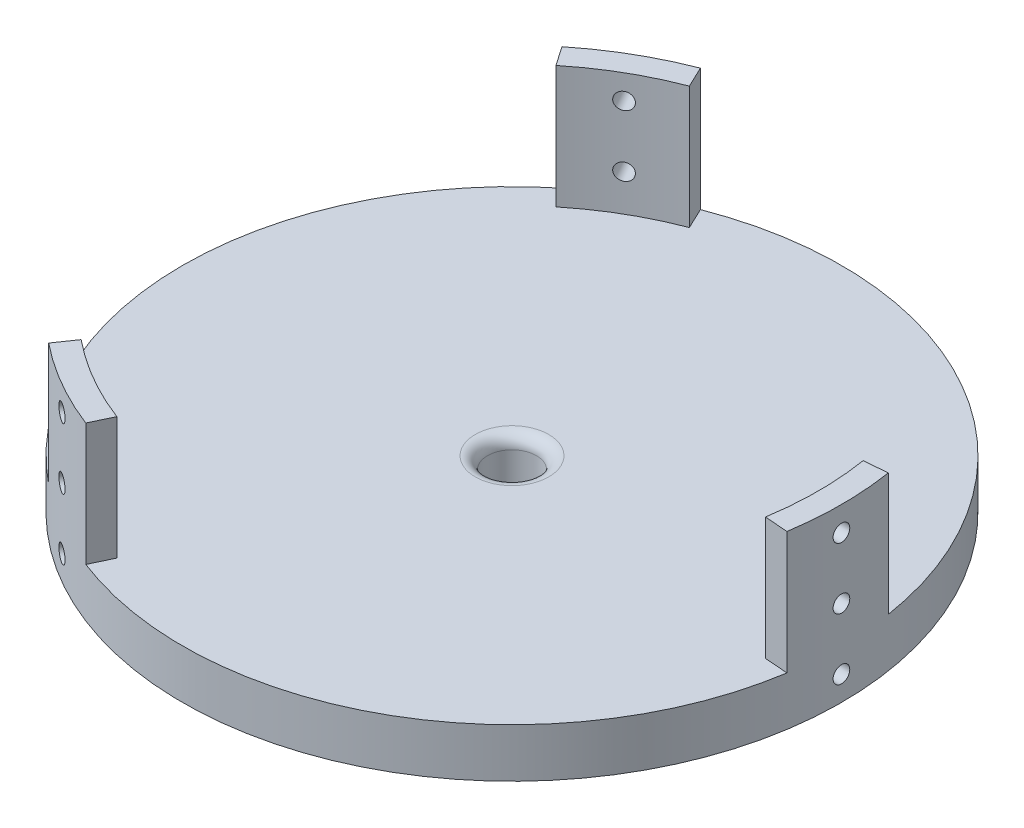
SolidWorks part; units mm, degrees
material "6061-T6 (SS)"
ref_plane "Front" through (0, 0, 0) normal (0, 0, 1) x (1, 0, 0)
ref_plane "Top" through (0, 0, 0) normal (0, 1, 0) x (1, 0, 0)
ref_plane "Right" through (0, 0, 0) normal (1, 0, 0) x (0, 0, -1)
sketch "Sketch1" plane through (0, 0, 0) normal (0, 1, 0) x (1, 0, 0)
  line L1 (0, 0) -> (127.635, 0)
  line L2 (0, 0) -> (0, 127.635)
  line L3 (0, 127.635) -> (127.635, 127.635)
  line L4 (127.635, 0) -> (127.635, 127.635)
  dimension "D1" = 127.635
  dimension "D2" = 127.635
extrude "Main Plate" add sketch "Sketch1" along normal blind 12.7
sketch "Sketch9" plane through (0, 12.7, 0) normal (0, 1, 0) x (1, 0, 0)
  circle A0 centre (63.8175, 63.8175) radius 85.725
  dimension "D1" = 171.45
extrude "Boss-Extrude1" add sketch "Sketch9" against normal up to surface (12.7 mm away) contours A0 up to face at (63.8175, 0, -63.8175)
sketch "Sketch10" plane through (0, 12.7, 0) normal (0, 1, 0) x (1, 0, 0)
  circle A0 centre (63.8175, 63.8175) radius 95.25
  circle A1 centre (63.8175, 63.8175) radius 85.4075
  dimension "D1" = 170.815
  dimension "D2" = 190.5
extrude "Cut-Extrude1" cut sketch "Sketch10" against normal blind 167.64 contours A0 | A1
sketch "Sketch14" plane through (0, 12.7, 0) normal (0, 1, 0) x (1, 0, 0)
  line L0 (201.1692, 63.8175) -> (-73.4523, 63.8175) construction
ref_plane "Plane1" through (0, 0, -63.8175) normal (0, 0, -1) x (-1, 0, 0)
ref_plane "Plane3" through (0, 6.35, 0) normal (0, 1, 0) x (1, 0, 0)
ref_plane "Plane2" through (-21.59, 0, 0) normal (-1, 0, 0) x (0, 0, 1)
sketch "Sketch18" plane through (0, 6.35, 0) normal (0, 1, 0) x (1, 0, 0)
  circle A0 centre (63.8175, 63.8175) radius 85.4075
  circle A1 centre (63.8175, 63.8175) radius 79.375
  circle A4 centre (63.8175, 63.8175) radius 85.4075 construction
  dimension "D1" = 158.75
extrude "Boss-Extrude2" add sketch "Sketch18" along normal blind 38.1
sketch "Sketch20" plane through (0, 12.7, 0) normal (0, 1, 0) x (1, 0, 0)
  line L0 (63.8175, 143.1925) -> (63.8175, -15.5575) construction
  line L1 (-15.5575, 63.8175) -> (143.1925, 63.8175) construction
  line L2 (63.8175, 63.8175) -> (-15.5575, -73.664) construction
  circle A0 centre (63.8175, 63.8175) radius 79.375 construction
  dimension "D1" = 30
ref_plane "Plane5" through (-15.5575, 12.7, 73.664) normal (-0.5, 0, 0.866) x (0.866, 0, 0.5)
sketch "Sketch15" plane through (166.2216, 0, 178.6143) normal (0.5, 0, -0.866) x (-0.866, 0, -0.5)
  line L3 (289.2754, 44.45) -> (130.5254, 44.45) construction
  line L4 (124.4929, 0) -> (295.3079, 0) construction
  line L6 (278.6412, 12.7) -> (141.1597, 12.7) construction
  circle A0 centre (209.9004, 22.225) radius 2.159
  circle A1 centre (209.9004, 38.1) radius 2.159
  circle A2 centre (209.9004, 6.35) radius 2.159
  point P16 (209.9004, 12.7)
  dimension "D1" = 4.318
  dimension "D2" = 15.875
  dimension "D3" = 4.318
  dimension "D4" = 4.318
  dimension "D5" = 6.35
  dimension "D6" = 6.35
  dimension "D7" = 0
extrude "Cut-Extrude3" cut sketch "Sketch15" along normal blind 88.9
pattern_circular "CirPattern1" count 3 over 360 about axis through (63.8175, -154.94, -63.8175) along (0, 1, 0) of "Cut-Extrude3" reverse direction yes
ref_plane "Plane4" through (63.8175, 0, 0) normal (-1, 0, 0) x (0, 0, 1)
sketch "Sketch23" plane through (0, 12.7, 0) normal (0, 1, 0) x (1, 0, 0)
  line L0 (13.6787, 125.352) -> (7.5523, 134.2379)
  line L1 (15.1867, 11.8815) -> (13.6787, 2.283) construction
  line L3 (-15.5575, 63.8175) -> (143.1925, 63.8175) construction
  line L4 (63.8175, 143.1925) -> (63.8175, -15.5575) construction
  line L5 (-15.5575, 63.8175) -> (143.1925, 63.8175)
  line L6 (63.8175, 143.1925) -> (63.8175, -15.5575)
  line L7 (13.6787, 2.283) -> (6.9592, -7.4631)
  line L8 (-19.2671, 125.3206) -> (-48.797, 60.3978)
  line L9 (-48.797, 60.3978) -> (-9.8843, 7.0525)
  line L10 (-9.8843, 7.0525) -> (6.9592, -7.4631)
  line L11 (24.1345, -4.9259) -> (13.6787, 2.283) construction
  line L14 (7.5523, 134.2379) -> (-19.2671, 125.3206)
  line L15 (24.1345, 132.5609) -> (13.6787, 125.352) construction
  line L28 (63.8175, 63.8175) -> (24.1345, -4.9259) construction
  line L29 (63.8175, 63.8175) -> (24.1345, 132.5609) construction
  line L30 (142.1773, 76.4717) -> (152.9359, 77.3344)
  line L31 (152.9359, 77.3344) -> (158.6231, 105.0193)
  line L32 (158.6231, 105.0193) -> (117.1632, 163.0543)
  line L33 (117.1632, 163.0543) -> (51.5085, 156.0277)
  line L34 (51.5085, 156.0277) -> (30.5159, 148.6985)
  line L35 (35.5964, 138.0062) -> (30.5159, 148.6985)
  line L36 (35.5964, -10.3712) -> (30.9643, -20.1198)
  line L37 (30.9643, -20.1198) -> (52.0965, -38.8874)
  line L38 (52.0965, -38.8874) -> (123.0863, -31.9996)
  line L39 (123.0863, -31.9996) -> (149.8284, 28.3723)
  line L40 (149.8284, 28.3723) -> (153.9775, 50.217)
  line L41 (142.1773, 51.1633) -> (153.9775, 50.217)
  circle A0 centre (63.8175, 63.8175) radius 79.375 construction
  arc A1 (13.6787, 2.283) -> (13.6787, 125.352) centre (63.8175, 63.8175) cw
  circle A3 centre (63.8175, 63.8175) radius 79.375
  arc A6 (35.5964, 138.0062) -> (142.1773, 76.4717) centre (63.8175, 63.8175) cw
  arc A7 (142.1773, 51.1633) -> (35.5964, -10.3712) centre (63.8175, 63.8175) cw
  circle A9 centre (63.8175, 63.8175) radius 79.375
  circle M15 centre (63.8175, 63.8175) radius 79.375
  dimension "D1" = 79.375
  dimension "D2" = 0
  dimension "D3" = 12.7
  dimension "D4" = 90
  dimension "D5" = 12.7
  dimension "D6" = 90
  dimension "D8" = 60.004
  dimension "D9" = 60.004
  dimension "D7" = 3
extrude "Cut-Extrude6" cut sketch "Sketch23" along normal blind 111.6 contours L9 L10 L7 L8 M15 | L34 L35 A6 L30 L31 L32 L33 | L40 L41 A7 L36 L37 L38 L39 region at (-18.2379, 12.7, -69.3048)
sketch "Sketch27" plane through (0, 0, 0) normal (0, -1, 0) x (1, 0, 0)
  circle A0 centre (63.8175, -63.8175) radius 15.24
  circle A1 centre (63.8175, -63.8175) radius 85.4075 construction
  circle A2 centre (63.8175, -63.8175) radius 6.35
  dimension "D1" = 30.48
  dimension "D2" = 12.7
ref_axis "Axis2" through (63.8175, 0, -63.8175) along (0, 1, 0)
extrude "Cut-Extrude7" cut sketch "Sketch27" against normal up to surface (12.7 mm away) contours A2 up to face at (63.8175, 12.7, -63.8175)
extrude "Boss-Extrude3" add sketch "Sketch27<3>" along normal blind 31.75
sketch "Sketch27<3>" plane through (0, 0, 0) normal (0, -1, 0) x (1, 0, 0) same geometry as "Sketch27"
fillet "Fillet1" radius 3.175 3 edges at (63.8175, -31.75, -79.0575) (63.8175, 0, -79.0575) (63.8175, 12.7, -70.1675)
